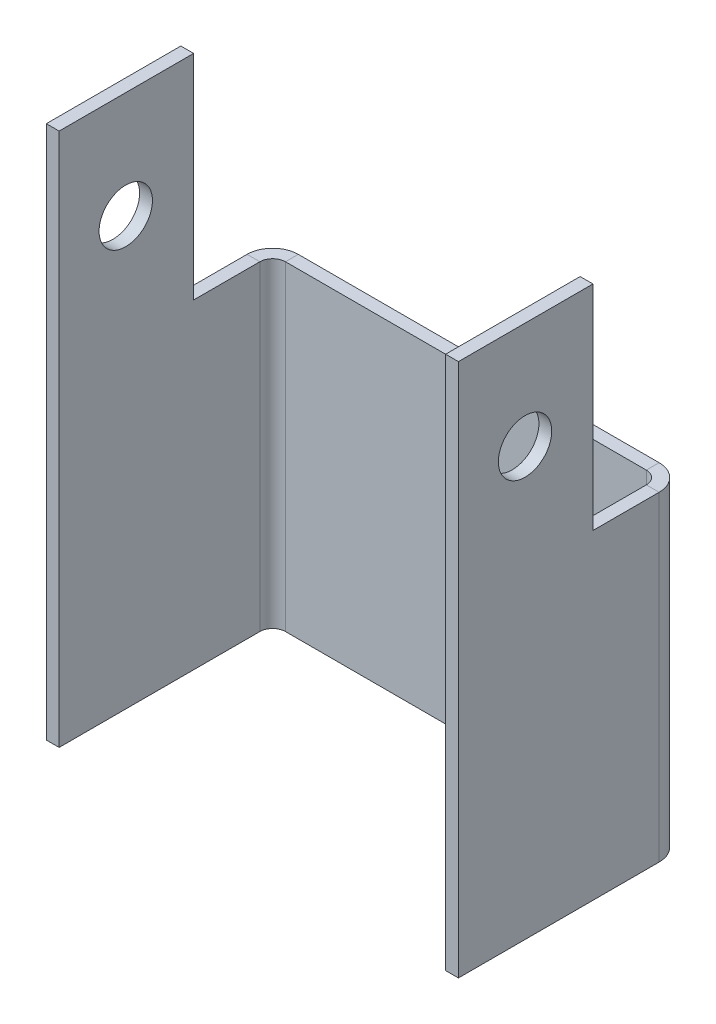
SolidWorks part; units mm, degrees
note: The reader was unsure of these and kept them because the rebuilt part matched: flange length of "Brida de arista1".
ref_plane "Alzado" through (0, 0, 0) normal (0, 0, 1) x (1, 0, 0)
ref_plane "Planta" through (0, 0, 0) normal (0, 1, 0) x (1, 0, 0)
ref_plane "Vista lateral" through (0, 0, 0) normal (1, 0, 0) x (0, 0, -1)
sketch "Croquis1" plane through (0, 0, 0) normal (0, 0, 1) x (1, 0, 0)
  line L1 (-24.511, 31.75) -> (24.511, 31.75)
  line L2 (-24.511, 31.75) -> (-24.511, -31.75)
  line L3 (-24.511, -31.75) -> (24.511, -31.75)
  line L4 (24.511, 31.75) -> (24.511, -31.75)
  line L5 (-24.511, 31.75) -> (24.511, -31.75) construction
  line L6 (-24.511, -31.75) -> (24.511, 31.75) construction
  point P0 (0, 0)
  dimension "D1" = 63.5
  dimension "D2" = 49.022
base flange "Brida base1" sketch "Croquis1" thickness 1.524 reverse thickness direction no parameters "D1"=0.508
edge flange "Brida de arista1" sketch "Croquis10" flange profiles "Croquis10", "Croquis11" flange angle 90 flange length 26.924 flange position material inside bend radius 1.524 thickness 1.524 relief rectangular parameters "D6"=10, "D8"=1
sketch "Croquis10" plane through (24.511, 0, 0) normal (-1, 0, 0) x (0, -1, 0)
  line L2 (-31.75, 0) -> (-31.75, 25.4)
  line L3 (-31.75, 25.4) -> (31.75, 25.4)
  line L4 (31.75, 25.4) -> (31.75, 0)
  line L5 (31.75, 0) -> (-31.75, 0) construction
  line L6 (31.75, 0) -> (-31.75, 0)
sketch "Croquis11" plane through (-24.511, 0, 0) normal (1, 0, 0) x (0, 1, 0)
  line L0 (31.75, 0) -> (-31.75, 0) construction
  line L1 (31.75, 0) -> (-31.75, 0)
  line L2 (31.75, 0) -> (31.75, 25.4)
  line L3 (31.75, 25.4) -> (-31.75, 25.4)
  line L4 (-31.75, 25.4) -> (-31.75, 0)
bend "Pliegue de arista1" bend radius 1.524 bend angle 90 parameters "D5"=1
bend "Pliegue de arista2" bend radius 1.524 bend angle 90 parameters "D5"=2
sketch "Croquis23" plane through (24.511, 0, 0) normal (1, 0, 0) x (0, 0, -1)
  line L0 (-9.398, 31.75) -> (-9.398, 6.35)
  line L1 (-25.4, 31.75) -> (-1.524, 31.75) construction
  line L2 (1.524, 31.75) -> (1.524, -31.75) construction
  line L3 (1.524, 6.35) -> (-9.398, 6.35)
  line L4 (-9.398, 31.75) -> (1.524, 31.75)
  line L5 (-1.524, -31.75) -> (-25.4, -31.75) construction
  line L6 (1.524, 6.35) -> (1.524, 31.75)
  line L7 (-25.4, -31.75) -> (-25.4, 31.75) construction
  circle A0 centre (-17.4752, 19.05) radius 3.175
  dimension "D5" = 6.35
  dimension "D1" = 10.922
  dimension "D2" = 38.1
  dimension "D3" = 7.9248
  dimension "D4" = 50.8
extrude "Cortar-Extruir4" cut sketch "Croquis23" against normal blind 73.66 normal cut yes
sketch "Líneas de pliegue1" [suppressed] plane through (0, 0, 0) normal (0, 1, 0) x (1, 0, 0)
sketch "Cuadro delimitador1" [suppressed] plane through (0, 0, 0) normal (0, 1, 0) x (1, 0, 0)
sheet metal parameters "Chapa metálica1" thickness 1.524 parameters "D1"=0.508
flat pattern "Chapa desplegada1" [suppressed]
sketch "Líneas de pliegue2" plane through (0, 0, 0) normal (0, 1, 0) x (1, 0, 0)
sketch3d "Cuadro delimitador2" [suppressed]
  line L0 (-24.511, 31.75, 0) -> (-24.511, -31.75, 0) construction
  line L1 (24.511, 31.75, 0) -> (24.511, -31.75, 0) construction
  line L2 (-24.511, 31.75, 0) -> (24.511, 31.75, 0) construction
  line L3 (-24.511, -31.75, 0) -> (24.511, -31.75, 0) construction
sheet metal parameters "Chapa metálica2" thickness 1.524 parameters "D1"=0.508
flat pattern "Chapa desplegada1" [suppressed]
sketch "Líneas de pliegue2" plane through (0, 0, 0) normal (0, 0, 1) x (1, 0, 0)
  line L0 (-23.2345, 31.75) -> (-23.2345, -31.75) construction
  line L1 (23.2345, -31.75) -> (23.2345, 31.75) construction
  line L2 (-23.2345, 31.75) -> (-23.2345, -31.75) construction
  line L3 (23.2345, -31.75) -> (23.2345, 31.75) construction
sketch3d "Cuadro delimitador2" [suppressed]
  line L0 (-48.882, -31.75, 0) -> (48.882, -31.75, 0) construction
  line L1 (-48.882, 31.75, 0) -> (48.882, 31.75, 0) construction
  line L2 (-48.882, -31.75, 0) -> (-48.882, 31.75, 0) construction
  line L3 (48.882, -31.75, 0) -> (48.882, 31.75, 0) construction
bend of the flat pattern "Aplanar-<Pliegue de arista1>1"
bend of the flat pattern "Aplanar-<Pliegue de arista2>1"
sketch "Croquis12-1" [suppressed] plane through (-23.482, 0, -1.524) normal (0, 0, -1) x (-1, 0, 0)
  line L0 (-1.524, 31.75) -> (14.351, 31.75)
  line L2 (14.351, 31.75) -> (14.351, 6.35)
  line L3 (25.4, -31.75) -> (-72.3639, -31.75) construction
  line L6 (14.351, 6.35) -> (-1.524, 6.35)
  line L8 (-1.524, 6.35) -> (-1.524, 31.75)
  dimension "D1" = 15.875
  dimension "D2" = 38.1
sketch "Croquis21-1" [suppressed] plane through (23.482, 0, -1.524) normal (0, 0, -1) x (-1, 0, 0)
  line L0 (-25.4, 31.75) -> (-9.652, 31.75)
  line L2 (-9.652, 31.75) -> (-9.652, 6.35)
  line L3 (-9.652, 6.35) -> (-25.4, 6.35)
  line L5 (-25.4, 6.35) -> (-25.4, 31.75)
  line L6 (72.3639, -31.75) -> (-25.4, -31.75) construction
  dimension "D1" = 38.1
  dimension "D2" = 15.748
sheet metal parameters "Chapa metálica8" thickness 1.524 parameters "D1"=0.508
flat pattern "Chapa desplegada1"
sketch "Líneas de pliegue2" plane through (0, 0, 0) normal (0, 0, 1) x (1, 0, 0)
  line L0 (-23.2345, 6.35) -> (-23.2345, -31.75) construction
  line L1 (23.2345, -31.75) -> (23.2345, 6.35) construction
  line L2 (-23.2345, 6.35) -> (-23.2345, -31.75) construction
  line L3 (23.2345, -31.75) -> (23.2345, 6.35) construction
sketch3d "Cuadro delimitador2" [suppressed]
  line L0 (-48.882, -31.75, 0) -> (48.882, -31.75, 0) construction
  line L1 (-48.882, 31.75, 0) -> (48.882, 31.75, 0) construction
  line L2 (-48.882, -31.75, 0) -> (-48.882, 31.75, 0) construction
  line L3 (48.882, -31.75, 0) -> (48.882, 31.75, 0) construction
bend of the flat pattern "Aplanar-<Pliegue de arista1>1"
bend of the flat pattern "Aplanar-<Pliegue de arista2>1"
